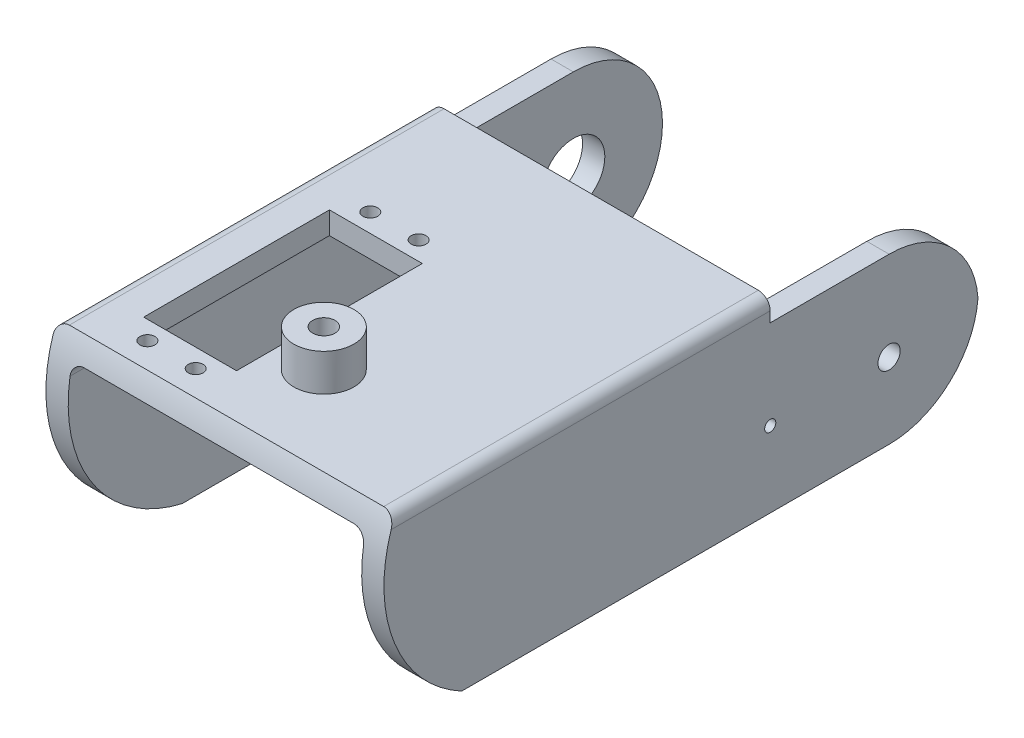
SolidWorks part; units mm, degrees
ref_plane "Front Plane" through (0, 0, 0) normal (0, 0, 1) x (1, 0, 0)
ref_plane "Top Plane" through (0, 0, 0) normal (0, 1, 0) x (1, 0, 0)
ref_plane "Right Plane" through (0, 0, 0) normal (1, 0, 0) x (0, 0, -1)
sketch "Sketch1" plane through (0, 0, 0) normal (0, 0, 1) x (1, 0, 0)
  line L0 (-36.0659, 24.6498) -> (36.1653, 24.6498)
  line L1 (36.1653, 24.6498) -> (36.1653, -15.3067)
  line L2 (36.1653, -15.3067) -> (31.4028, -15.3067)
  line L3 (31.4028, -15.3067) -> (31.4028, 19.8873)
  line L4 (31.4028, 19.8873) -> (-31.3034, 19.8873)
  line L5 (-31.3034, 19.8873) -> (-31.3034, -18.2127)
  line L6 (-31.3034, -18.2127) -> (-36.0659, -18.2127)
  line L7 (-36.0659, -18.2127) -> (-36.0659, 24.6498)
extrude "Boss-Extrude1" add sketch "Sketch1" along normal blind 101.6
sketch "Sketch2" plane through (0, 0, 0) normal (0, 0, -1) x (-1, 0, 0)
  line L0 (-31.4028, 19.8873) -> (-36.1653, 19.8873)
  line L1 (-36.1653, -15.3067) -> (-36.1653, 24.6498) construction
  line L2 (-36.1653, 19.8873) -> (-36.1653, -15.3067)
  line L3 (-36.1653, -15.3067) -> (-31.4028, -15.3067)
  line L4 (-31.4028, -15.3067) -> (-31.4028, 19.8873)
  line L5 (31.3034, 19.8873) -> (36.0659, 19.8873)
  line L6 (36.0659, 24.6498) -> (36.0659, -18.2127) construction
  line L7 (36.0659, 19.8873) -> (36.0659, -18.2127)
  line L8 (36.0659, -18.2127) -> (31.3034, -18.2127)
  line L9 (31.3034, -18.2127) -> (31.3034, 19.8873)
  line M1 (36.0659, -18.2127) -> (36.0659, 24.6498)
  line M7 (31.3034, 19.8873) -> (31.3034, -18.2127)
  line M8 (31.3034, -18.2127) -> (36.0659, -18.2127)
extrude "Boss-Extrude2" add sketch "Sketch2" along normal blind 44.45 contours L5 M7 M8 M1 | L4 L0 L2 L3 region at (-33.6847, 0.8373, 0)
fillet "Fillet1" radius 19.05 4 edges at (-33.6847, -18.2127, -44.45) (-33.6847, 19.8873, -44.45) (33.7841, -15.3067, -44.45) (33.7841, 19.8873, -44.45)
fillet "Fillet4" radius 2.54 4 edges at (31.4028, 19.8873, 50.8) (-31.3034, 19.8873, 50.8) (36.1653, 24.6498, 50.8) (-36.0659, 24.6498, 50.8)
fillet "Fillet5" radius 2.54 2 edges at (33.7841, -15.3067, 101.6) (-33.6847, -18.2127, 101.6)
sketch "Sketch4" plane through (-36.0659, 0, 0) normal (-1, 0, 0) x (0, 0, 1)
  line L0 (-12.7, 19.8873) -> (-12.7, -18.2127) construction
  line L1 (-25.4, 19.8873) -> (0, 19.8873) construction
  line L2 (99.06, -18.2127) -> (-25.4, -18.2127) construction
  line L3 (-12.7, 0.8373) -> (101.6, 0.8373) construction
  line L4 (101.6, 22.1098) -> (101.6, -15.6727) construction
  line L5 (101.6, 0.8373) -> (-25.4, 0.8373) construction
  line L6 (-25.4, 0.8373) -> (0, 0.8373) construction
  circle A0 centre (-25.4, 0.8373) radius 1.1906
  circle A1 centre (0, 0.8373) radius 1.1906
  dimension "D1" = 25.4
extrude "Cut-Extrude1" cut sketch "Sketch4" against normal through all
sketch "Sketch5" plane through (0, 24.6498, 0) normal (0, 1, 0) x (1, 0, 0)
  line L0 (-17.1395, -101.6) -> (-17.1395, -50.8) construction
  line L1 (33.6253, -101.6) -> (-33.5259, -101.6) construction
  line L2 (-17.1395, -50.8) -> (33.6253, -50.8) construction
  line L3 (33.6253, -101.6) -> (33.6253, 0) construction
  line L4 (-17.1395, -30.9562) -> (-17.1395, -26.9875) construction
  line L5 (-27.0614, -70.6438) -> (-7.2176, -70.6438)
  line L6 (-27.0614, -70.6438) -> (-27.0614, -30.9562)
  line L7 (-27.0614, -30.9562) -> (-7.2176, -30.9562)
  line L8 (-7.2176, -70.6438) -> (-7.2176, -30.9562)
  line L9 (-27.0614, -70.6438) -> (-7.2176, -30.9562) construction
  line L10 (-27.0614, -30.9562) -> (-7.2176, -70.6438) construction
  line L11 (-17.1395, -26.9875) -> (-22.2989, -26.9875) construction
  circle A0 centre (-22.2989, -26.9875) radius 1.5875
  circle A1 centre (-11.9801, -26.9875) radius 1.5875
  circle A2 centre (-11.9801, -74.6125) radius 1.5875
  circle A3 centre (-22.2989, -74.6125) radius 1.5875
  dimension "D1" = 19.8438
  dimension "D2" = 39.6875
  dimension "D3" = 50.8
  dimension "D4" = 3.9688
  dimension "D5" = 5.1594
extrude "Cut-Extrude2" cut sketch "Sketch5" against normal through all
sketch "Sketch6" plane through (0, 24.6498, 0) normal (0, 1, 0) x (1, 0, 0)
  line L0 (-17.1395, -70.6438) -> (-17.1395, -61.1188) construction
  line L1 (-27.0614, -70.6438) -> (-7.2176, -70.6438) construction
  line L2 (-17.1395, -61.1188) -> (1.9105, -61.1188) construction
  circle A0 centre (1.9105, -61.1188) radius 2.3812
  circle A1 centre (1.9105, -61.1188) radius 6.4181
  dimension "D1" = 9.525
  dimension "D2" = 19.05
extrude "Boss-Extrude3" add sketch "Sketch6" along normal blind 7.9375
sketch "Sketch7" plane through (0, 24.6498, 0) normal (0, 1, 0) x (1, 0, 0)
  circle A0 centre (1.9105, -61.1188) radius 2.3812
extrude "Cut-Extrude3" cut sketch "Sketch7" against normal through all
sketch "Sketch8" plane through (36.1653, 0, 0) normal (1, 0, 0) x (0, 0, -1)
  circle A0 centre (0, 0.8373) radius 1.1906
  circle A1 centre (25.4, 0.8373) radius 2.3813
extrude "Cut-Extrude4" cut sketch "Sketch8" against normal blind 12.7
sketch "Sketch9" plane through (-36.0659, 0, 0) normal (-1, 0, 0) x (0, 0, 1)
  line L0 (-25.4, 0.8373) -> (0, 0.8373) construction
  line L1 (-25.1012, 5.5904) -> (0, 4.0123) construction
  line L2 (-25.1012, -3.9158) -> (0, -2.3377) construction
  line L3 (-25.0693, 6.0974) -> (0.0165, 4.5203)
  line L4 (-25.0693, -4.4228) -> (0.0165, -2.8456)
  arc A0 (-25.1012, 5.5904) -> (-25.1012, -3.9158) centre (-25.4, 0.8373) ccw construction
  arc A1 (0, -2.3377) -> (0, 4.0123) centre (0, 0.8373) ccw construction
  arc A2 (0.0165, -2.8456) -> (0.0165, 4.5203) centre (0, 0.8373) ccw
  arc A3 (-25.0693, 6.0974) -> (-25.0693, -4.4228) centre (-25.4, 0.8373) ccw
  dimension "D1" = 0.508
extrude "Cut-Extrude5" cut sketch "Sketch9" against normal blind 2.3813
sketch "Sketch10" plane through (-31.3034, 0, 0) normal (1, 0, 0) x (0, 0, -1)
  circle A0 centre (25.4, 0.8373) radius 6.731
extrude "Cut-Extrude6" cut sketch "Sketch10" against normal through all
sketch "Sketch11" plane through (-36.0659, 0, 0) normal (-1, 0, 0) x (0, 0, 1)
  line L1 (78.2309, 28.2857) -> (107.145, 28.2857)
  line L2 (47.4346, -18.812) -> (47.4346, -25.579)
  line L3 (47.4346, -25.579) -> (107.145, -25.579)
  line L4 (107.145, 28.2857) -> (107.145, -25.579)
  arc A0 (47.4346, -18.812) -> (78.2309, 28.2857) centre (51.0849, 12.4186) ccw
extrude "Cut-Extrude7" cut sketch "Sketch11" against normal through all
